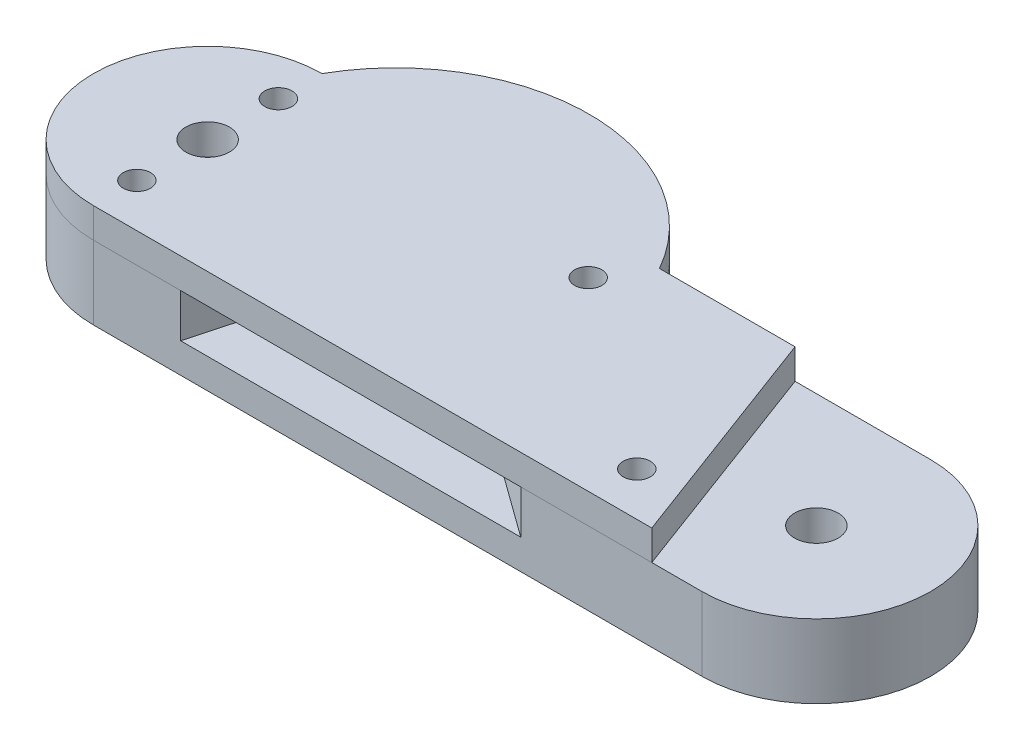
SolidWorks part; units mm, degrees
ref_plane "Front Plane" through (0, 0, 0) normal (0, 0, 1) x (1, 0, 0)
ref_plane "Top Plane" through (0, 0, 0) normal (0, 1, 0) x (1, 0, 0)
ref_plane "Right Plane" through (0, 0, 0) normal (1, 0, 0) x (0, 0, -1)
sketch "Sketch1" plane through (0, 0, 0) normal (0, 1, 0) x (1, 0, 0)
  line L0 (0, -10.5004) -> (-55.9305, -10.5004)
  line L1 (0, 10.5004) -> (-55.9305, 10.5004)
  line L5 (0, 11.5004) -> (-55.9305, 11.5004) construction
  line L6 (0, -11.5004) -> (-55.9305, -11.5004) construction
  circle A0 centre (0, 0) radius 2
  arc A1 (0, -10.5004) -> (0, 10.5004) centre (0, 0) ccw
  arc A2 (-55.9305, 10.5004) -> (-55.9305, -10.5004) centre (-55.9305, 0) ccw
  circle A3 centre (-55.9305, 0) radius 2
  arc A7 (0, -11.5004) -> (0, 11.5004) centre (0, 0) ccw construction
  arc A8 (-55.9305, 11.5004) -> (-55.9305, -11.5004) centre (-55.9305, 0) ccw construction
  arc A9 (-67.2423, -5.04) -> (-54.9145, -15.6487) centre (-55.7741, -4.1805) ccw construction
  arc A10 (-55.9305, 10.5004) -> (-55.9305, -10.5004) centre (-55.9305, 0) ccw construction
  circle A11 centre (0, 0) radius 67.4309 construction
  arc A12 (-59.8966, 30.973) -> (-67.2423, -5.04) centre (0, 0) ccw construction
  dimension "D1" = 4
  dimension "D2" = 1
  dimension "D3" = 4
extrude "Boss-Extrude1" add sketch "Sketch1" along normal mid plane 9.5
sketch "Sketch3" plane through (0, 0, 0) normal (0, 1, 0) x (1, 0, 0)
  line L0 (0, 0) -> (-47.1525, -15.3208) construction
  line L1 (0, 0) -> (24.7895, -42.9367) construction
  line L2 (0, 0) -> (-55.9305, 0) construction
  line L3 (24.7895, -42.9367) -> (-41.5934, 5.0595) construction
  line L4 (-41.5934, 5.0595) -> (-47.1525, -15.3208) construction
  line L5 (-41.5934, 5.0595) -> (-37.6461, 19.5308) construction
  line L6 (-41.5934, 5.0595) -> (-53.749, 13.8482) construction
  line L7 (22.8477, -44.0007) -> (-38.0092, 0) construction
  line L8 (-35.7518, 18.8753) -> (-39.2995, 5.869)
  line L9 (-43.8873, 4.25) -> (-54.8123, 12.149)
  line L11 (26.6452, -41.8104) -> (-39.2995, 5.869)
  line L12 (-39.6108, 19.9279) -> (-42.7627, 8.3729) construction
  line L13 (-42.7627, 8.3729) -> (-52.4686, 15.3905) construction
  line L14 (-40.9004, 0) -> (-45.9674, -18.5763) construction
  line L15 (-43.8873, 4.25) -> (-48.2065, -11.585)
  line L18 (-40.4216, 6.6802) -> (-50.8477, 14.2185) construction
  line L20 (-41.5934, 5.0595) -> (-52.0196, 12.5978) construction
  line L21 (-42.7652, 3.4387) -> (-53.1914, 10.977) construction
  line L23 (-43.5229, 5.5858) -> (-49.082, -14.7945) construction
  line L26 (-39.6639, 4.5332) -> (-45.223, -15.8471) construction
  line L27 (25.9613, -41.316) -> (-40.4216, 6.6802) construction
  line L28 (23.6177, -44.5574) -> (-42.7652, 3.4387) construction
  arc A1 (-48.2065, -11.585) -> (26.6452, -41.8104) centre (0, 0) ccw
  arc A4 (-55.9305, 10.5004) -> (-55.9305, -10.5004) centre (-55.9305, 0) ccw construction
  arc A7 (-35.7518, 18.8753) -> (-54.8123, 12.149) centre (-41.5934, 5.0595) ccw
  dimension "D1" = 99.1581
  dimension "D3" = 120
  dimension "D6" = 30
  dimension "D2" = 18
  dimension "D4" = 2
  dimension "D5" = 2
extrude "Cut-Extrude1" cut sketch "Sketch3" against normal mid plane 4
sketch "Sketch5" plane through (0, 0, 0) normal (0, 1, 0) x (1, 0, 0)
  line L0 (-40.4241, 1.7461) -> (-52.5322, 10.5004) construction
  line L1 (-40.4241, 1.7461) -> (-35.7382, 18.9254) construction
  line L2 (-52.5322, 10.5004) -> (-43.8873, 4.25) construction
  line L3 (-39.2995, 5.869) -> (-38.0362, 10.5004) construction
  line L4 (-55.9305, 10.5004) -> (-24.9177, 10.5004)
  line L5 (0, 10.5004) -> (-55.9305, 10.5004) construction
  circle A0 centre (-40.4241, 1.7461) radius 17.807
extrude "Boss-Extrude2" add sketch "Sketch5" along normal up to surface and the other way up to surface contours A0 region at (-40.4241, 0, -14.2141) up to face at (0, 4.75, 2) other way up to face at (-27.9653, -4.75, 0)
sketch "Sketch6" plane through (0, 0, 0) normal (0, 1, 0) x (1, 0, 0)
  line L0 (-39.2995, 5.869) -> (-16.6593, -10.5004)
  line L1 (-47.9107, -10.5004) -> (-43.8873, 4.25)
  line L2 (-43.8873, 4.25) -> (-54.8544, 12.1794)
  line L3 (-39.2995, 5.869) -> (-35.7382, 18.9254)
  line L4 (-16.6593, -10.5004) -> (-39.2995, 5.869) construction
  line L5 (-43.8873, 4.25) -> (-47.9107, -10.5004) construction
  line L6 (-52.5322, 10.5004) -> (-43.8873, 4.25) construction
  line L7 (-39.2995, 5.869) -> (-38.0362, 10.5004) construction
  line L8 (-55.9305, -10.5004) -> (0, -10.5004) construction
  line L9 (-16.6593, -10.5004) -> (-47.9107, -10.5004)
  arc A0 (-24.9177, 10.5004) -> (-55.9305, 10.5004) centre (-40.4241, 1.7461) ccw construction
  arc A1 (-35.7382, 18.9254) -> (-54.8544, 12.1794) centre (-40.4241, 1.7461) ccw
extrude "Cut-Extrude2" cut sketch "Sketch6" against normal mid plane 4
sketch "Sketch7" plane through (0, -4.75, 0) normal (0, -1, 0) x (1, 0, 0)
  line L0 (0, 0) -> (4.5965, 4.5965) construction
  line L1 (0, 0) -> (6.5004, 0) construction
  line L4 (0, 6.5004) -> (-55.9305, 6.5004)
  line L5 (-27.4616, -6.5004) -> (0, -6.5004)
  line L6 (0, 6.5004) -> (-55.9305, 6.5004) construction
  line L7 (-55.9305, -6.5004) -> (0, -6.5004) construction
  circle A3 centre (-27.4616, -6.5004) radius 1.25
  circle A4 centre (0, -6.5004) radius 1.25 construction
  circle A5 centre (4.5965, 4.5965) radius 1.25 construction
  arc A6 (0, -6.5004) -> (0, 6.5004) centre (0, 0) ccw
  arc A7 (-55.9305, 6.5004) -> (-53.5442, -6.0466) centre (-55.9305, 0) ccw
  arc A8 (-53.5442, -6.0466) -> (-27.4616, -6.5004) centre (-40.4241, -1.7461) ccw
  arc A9 (0, -6.5004) -> (0, 6.5004) centre (0, 0) ccw construction
  arc A10 (-55.9305, 6.5004) -> (-53.5442, -6.0466) centre (-55.9305, 0) ccw construction
  arc A11 (-53.5442, -6.0466) -> (-27.4616, -6.5004) centre (-40.4241, -1.7461) ccw construction
  circle A12 centre (-10, 6.5004) radius 1.25
  circle A13 centre (-55.9305, 6.5004) radius 1.25
  circle A14 centre (-55.9305, -6.5004) radius 1.25
  dimension "D4" = 2.5
  dimension "D2" = 10
  dimension "D3" = 45
  dimension "D1" = 4
extrude "Cut-Extrude3" cut sketch "Sketch7" against normal through all
sketch "Sketch8" plane through (0, -4.75, 0) normal (0, -1, 0) x (1, 0, 0)
  circle A0 centre (-55.9305, 6.5004) radius 2.75
  circle A1 centre (-55.9305, -6.5004) radius 2.75
  circle A2 centre (-27.4616, -6.5004) radius 2.75
  circle A3 centre (-10, 6.5004) radius 2.75
  dimension "D1" = 5.5
extrude "Cut-Extrude4" cut sketch "Sketch8" against normal blind 3.2
ref_plane "Plane1" through (0, 2, 0) normal (0, -1, 0) x (-1, 0, 0)
sketch "Sketch9" plane through (0, 4.75, 0) normal (0, 1, 0) x (1, 0, 0)
  line L0 (-12.4589, 10.5004) -> (-4.6195, -10.5004)
  line L1 (0, 10.5004) -> (-24.9177, 10.5004) construction
  line L2 (-55.9305, -10.5004) -> (0, -10.5004) construction
  line L3 (-6.5881, -5.2268) -> (-10, -6.5004) construction
  line L4 (-4.6195, -10.5004) -> (0, -10.5004)
  line L5 (-12.4589, 10.5004) -> (0, 10.5004)
  circle A0 centre (0, 0) radius 8 construction
  circle A1 centre (-10, -6.5004) radius 1.25 construction
  circle A2 centre (-10, -6.5004) radius 1.25 construction
  arc A3 (0, -10.5004) -> (0, 10.5004) centre (0, 0) ccw
  arc A4 (0, -10.5004) -> (0, 10.5004) centre (0, 0) ccw construction
  dimension "D1" = 16
extrude "Cut-Extrude5" cut sketch "Sketch9" against normal up to surface (2.75 mm away) up to face at (-39.9005, 2, -3.8681)
split "Split1" trim tools "Plane1" bodies to split 113 resulting bodies 111 112
